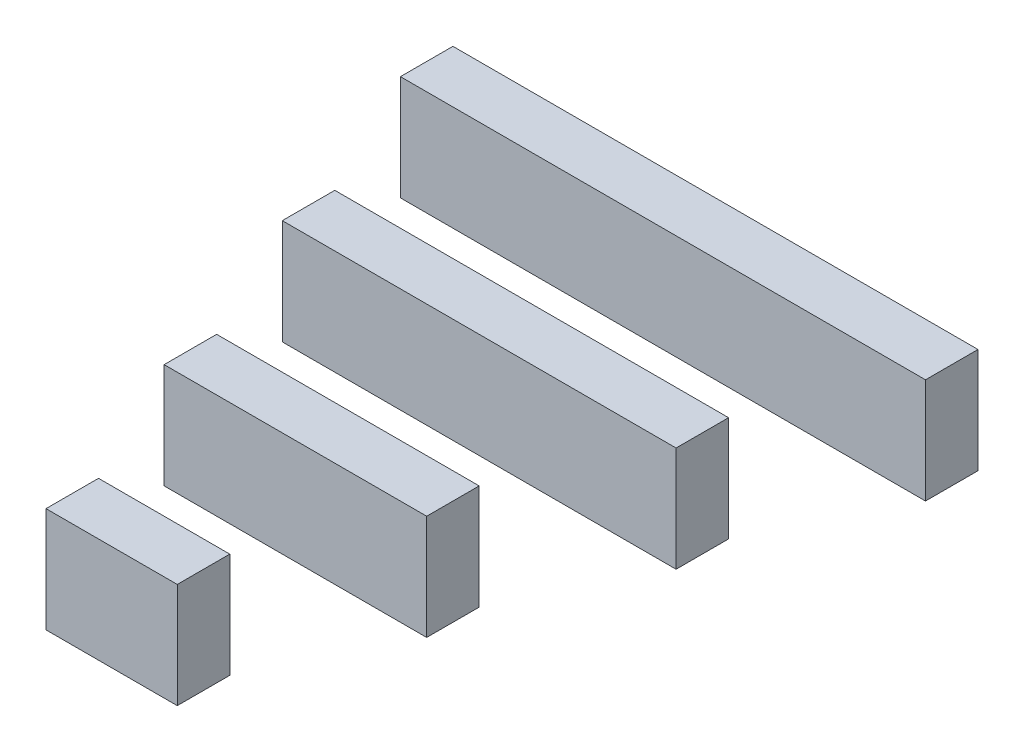
SolidWorks part; units mm, degrees
ref_plane "Front Plane" through (0, 0, 0) normal (0, 0, 1) x (1, 0, 0)
ref_plane "Top Plane" through (0, 0, 0) normal (0, 1, 0) x (1, 0, 0)
ref_plane "Right Plane" through (0, 0, 0) normal (1, 0, 0) x (0, 0, -1)
ref_plane "Plane1" through (0, 1, 0) normal (0, 1, 0) x (1, 0, 0)
sketch "Sketch1" plane through (0, 0, 0) normal (0, 1, 0) x (1, 0, 0)
  line L1 (25, -25) -> (-25, -25)
  line L2 (25, -25) -> (25, 25)
  line L3 (25, 25) -> (-25, 25)
  line L4 (-25, -25) -> (-25, 25)
  line L5 (25, -25) -> (-25, 25) construction
  line L6 (25, 25) -> (-25, -25) construction
  point P0 (0, 0)
  dimension "D1" = 50
  dimension "D2" = 50
sketch "Sketch5" plane through (0, 1, 0) normal (0, 1, 0) x (1, 0, 0)
  line L0 (-25, -25) -> (-25, 25) construction
  line L1 (-5, -19) -> (5, -19)
  line L2 (-5, -19) -> (-5, -23)
  line L3 (-5, -23) -> (5, -23)
  line L4 (5, -19) -> (5, -23)
  line L5 (-10, -5) -> (10, -5)
  line L6 (-10, -5) -> (-10, -9)
  line L7 (-10, -9) -> (10, -9)
  line L8 (10, -5) -> (10, -9)
  line L9 (-15, 9) -> (15, 9)
  line L10 (-15, 9) -> (-15, 5)
  line L11 (-15, 5) -> (15, 5)
  line L12 (15, 9) -> (15, 5)
  line L13 (-20, 23) -> (20, 23)
  line L14 (-20, 23) -> (-20, 19)
  line L15 (-20, 19) -> (20, 19)
  line L16 (20, 23) -> (20, 19)
  line L17 (25, -25) -> (-25, -25) construction
  dimension "D1" = 4
  dimension "D2" = 4
  dimension "D3" = 4
  dimension "D4" = 4
  dimension "D5" = 10
  dimension "D6" = 20
  dimension "D7" = 30
  dimension "D8" = 40
  dimension "D9" = 5
  dimension "D10" = 10
  dimension "D11" = 15
  dimension "D12" = 20
  dimension "D13" = 2
  dimension "D14" = 10
  dimension "D15" = 10
  dimension "D16" = 10
extrude "Boss-Extrude4" add sketch "Sketch5" along normal blind 8
